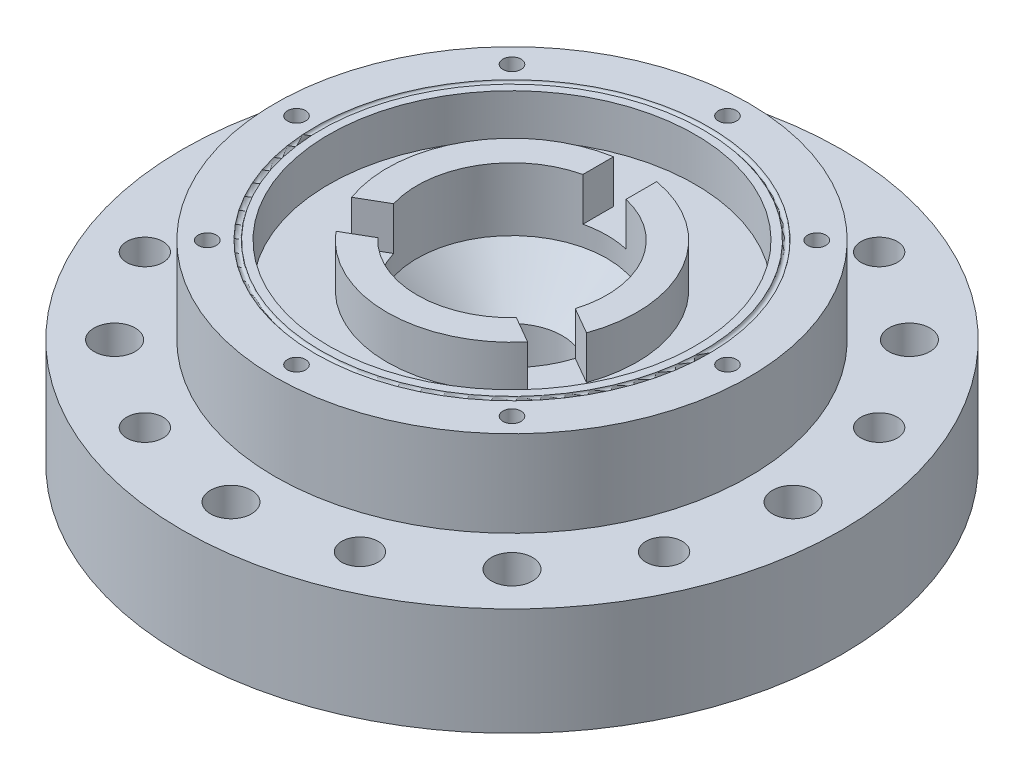
SolidWorks part; units mm, degrees
material "AISI 1020"
ref_plane "Front Plane" through (0, 0, 0) normal (0, 0, 1) x (1, 0, 0)
ref_plane "Top Plane" through (0, 0, 0) normal (0, 1, 0) x (1, 0, 0)
ref_plane "Right Plane" through (0, 0, 0) normal (1, 0, 0) x (0, 0, -1)
sketch "Sketch3" plane through (0, 0, 0) normal (1, 0, 0) x (0, 0, -1)
  line L2 (76.5, 15) -> (55, 15)
  line L3 (55, 15) -> (55, 35)
  line L4 (55, 35) -> (22.025, 35)
  line L7 (11.665, 0) -> (16.665, 0)
  line L8 (76.5, 15) -> (76.5, -10)
  line L9 (53.85, -10) -> (53.85, 86.2223) construction
  line L10 (76.5, -10) -> (53.85, -10)
  line L11 (11.665, 0) -> (11.665, 10)
  line L12 (11.665, 10) -> (22.025, 20.36)
  line L13 (22.025, 20.36) -> (22.025, 35)
  line L14 (0, 0) -> (0, 51.2471) construction
  line L15 (11.665, 10) -> (19.7366, 10) construction
  line L16 (65.2, -29.1535) -> (65.2, 61.9555) construction
  line L17 (0, 0) -> (11.665, 0) construction
  arc A3 (53.85, -10) -> (16.665, 0) centre (30.7197, -21.8739) ccw
  dimension "D6" = 26
  dimension "D1" = 10
  dimension "D2" = 55
  dimension "D3" = 76.5
  dimension "D4" = 45
  dimension "D5" = 53.85
  dimension "D7" = 11.665
  dimension "D9" = 25
  dimension "D11" = 10
  dimension "D12" = 45
  dimension "D13" = 44.05
  dimension "D14" = 5
  dimension "D15" = 65.2
revolve "Revolve1" add sketch "Sketch3" angle 360 about L14
sketch "Sketch4" plane through (0, 0, 0) normal (0, 1, 0) x (1, 0, 0)
  line L0 (0, 0) -> (-65.2, 0) construction
  circle A0 centre (-65.2, 0) radius 4.7625
  dimension "D2" = 9.525
  dimension "D1" = 65.2
extrude "Cut-Extrude2" cut sketch "Sketch4" along normal through all both and the other way through all contours A0
pattern_circular "CirPattern1" count 8 over 360 about axis through (0, 0, 0) along (0, 1, 0) of "Cut-Extrude2" reverse direction yes
sketch "Sketch6" plane through (0, 35, 0) normal (0, 1, 0) x (1, 0, 0)
  circle A0 centre (0, 0) radius 29
  circle A1 centre (0, 0) radius 42.5
  point P19 (0, 0)
  dimension "D1" = 58
  dimension "D2" = 85
extrude "Cut-Extrude3" cut sketch "Sketch6" against normal blind 10
sketch "Sketch7" plane through (0, 35, 0) normal (0, 1, 0) x (1, 0, 0)
  line L0 (0, 0) -> (0, 29) construction
  line L1 (-5, 29) -> (5, 29)
  line L2 (5, 29) -> (5, 21.45)
  line L3 (5, 21.45) -> (-5, 21.45)
  line L4 (-5, 21.45) -> (-5, 29)
  circle A0 centre (0, 0) radius 29 construction
  circle A1 centre (0, 0) radius 22.025 construction
  point P8 (0, 29)
  dimension "D1" = 10
extrude "Cut-Extrude4" cut sketch "Sketch7" against normal blind 10
pattern_circular "CirPattern2" count 3 over 360 about axis through (0, 0, 0) along (0, 1, 0) of "Cut-Extrude4" reverse direction yes
sketch "Sketch9" plane through (0, 35, 0) normal (0, 1, 0) x (1, 0, 0)
  line L0 (0, 0) -> (46.194, 19.1342) construction
  line L1 (0, 0) -> (100.5921, 0) construction
  circle A0 centre (46.194, 19.1342) radius 2
  dimension "D2" = 4
  dimension "D1" = 50
  dimension "D3" = 22.5
sketch "Sketch10" plane through (0, 35, 0) normal (0, 1, 0) x (1, 0, 0)
  circle A2 centre (0, 0) radius 45
  dimension "D1" = 90
sketch "Sketch11" plane through (0, 15, 0) normal (0, 1, 0) x (1, 0, 0)
  line L0 (-46.1034, 46.1034) -> (-65.2, 0) construction
  line L1 (0, 0) -> (-88.6644, 36.726) construction
  circle A0 centre (0, 0) radius 65.2 construction
  dimension "D1" = 130.4
hole_wizard "Tap Drill for 3/8-24 Tap1" positions "Sketch14" profile "Sketch15" hole size "3/8-24" standard "ANSI Inch"
sketch "Sketch14" plane through (0, 15, 0) normal (0, 1, 0) x (1, 0, 0)
  line L0 (0, 0) -> (-88.6644, 36.726) construction
  circle A0 centre (0, 0) radius 65.2 construction
  point P0 (-60.2369, 24.951)
  dimension "D1" = 65.2
sketch "Sketch15" plane through (-60.2369, 15, -24.951) normal (1, 0, 0) x (0, 0, 1)
  line L0 (0, 0) -> (0, 27.5335)
  line L1 (0, 27.5335) -> (4.2164, 25)
  line L2 (4.2164, 25) -> (4.2164, 0)
  line L5 (4.2164, 0) -> (0, 0)
  line L10 (0, 27.5335) -> (-4.2164, 25) construction
  line L11 (0, -6.35) -> (0, 107.95) construction
  dimension "Hole Dia." = 8.4328
  dimension "Hole Depth" = 25
  dimension "Drill Angle" = 118
cosmetic thread "Cosmetic Thread17" parameters "D2"=9.525
pattern_circular "CirPattern4" count 8 over 360 about axis through (0, 0, 0) along (0, -1, 0) of "Tap Drill for 3/8-24 Tap1"
cosmetic thread "Cosmetic Thread18" parameters "D2"=9.525
cosmetic thread "Cosmetic Thread19" parameters "D2"=9.525
cosmetic thread "Cosmetic Thread20" parameters "D2"=9.525
cosmetic thread "Cosmetic Thread21" parameters "D2"=9.525
cosmetic thread "Cosmetic Thread22" parameters "D2"=9.525
cosmetic thread "Cosmetic Thread23" parameters "D2"=9.525
cosmetic thread "Cosmetic Thread24" parameters "D2"=9.525
sketch "Sketch16" plane through (0, 35, 0) normal (0, 1, 0) x (1, 0, 0)
  circle A0 centre (0, 0) radius 50 construction
  dimension "D1" = 100
hole_wizard "Tap Drill for M5x0.8 Tap1" positions "Sketch24" profile "Sketch20" hole size "M5x0.8" standard "ANSI Metric"
sketch "Sketch24" plane through (0, 35, 0) normal (0, 1, 0) x (1, 0, 0)
  circle A0 centre (0, 0) radius 50 construction
  point P0 (-50, 0)
sketch "Sketch20" plane through (-50, 35, 0) normal (1, 0, 0) x (0, 0, 1)
  line L0 (0, 0) -> (0, 21.2618)
  line L1 (0, 21.2618) -> (2.1, 20)
  line L2 (2.1, 20) -> (2.1, 0)
  line L5 (2.1, 0) -> (0, 0)
  line L10 (0, 21.2618) -> (-2.1, 20) construction
  line L11 (0, -6.35) -> (0, 107.95) construction
  dimension "Hole Dia." = 4.2
  dimension "Hole Depth" = 20
  dimension "Drill Angle" = 118
cosmetic thread "Cosmetic Thread25" parameters "D2"=5.4864
pattern_circular "CirPattern5" count 8 over 360 about axis through (0, 0, 0) along (0, -1, 0) of "Tap Drill for M5x0.8 Tap1"
cosmetic thread "Cosmetic Thread26" parameters "D2"=5.4864
cosmetic thread "Cosmetic Thread27" parameters "D2"=5.4864
cosmetic thread "Cosmetic Thread28" parameters "D2"=5.4864
cosmetic thread "Cosmetic Thread29" parameters "D2"=5.4864
cosmetic thread "Cosmetic Thread30" parameters "D2"=5.4864
cosmetic thread "Cosmetic Thread31" parameters "D2"=5.4864
cosmetic thread "Cosmetic Thread32" parameters "D2"=5.4864
sketch "Sketch25" plane through (0, -10, 0) normal (0, -1, 0) x (1, 0, 0)
  circle A0 centre (0, 0) radius 53.85
  circle A1 centre (0, 0) radius 56.85
  dimension "D1" = 3
extrude "Boss-Extrude1" add sketch "Sketch25" along normal blind 6
fillet "Fillet1" radius 10 1 edges at (0, -10, -53.85)
sketch "Sketch26" plane through (0, -10, 0) normal (0, -1, 0) x (1, 0, 0)
  circle A0 centre (0, 0) radius 58
  dimension "D1" = 116
sweep "Cut-Sweep1" cut path "Sketch26" circular profile diameter 1.25 parameters "D3"=1.25
sweep "Cut-Sweep2" cut path "Sketch10" circular profile diameter 1.25 parameters "D3"=1.25
